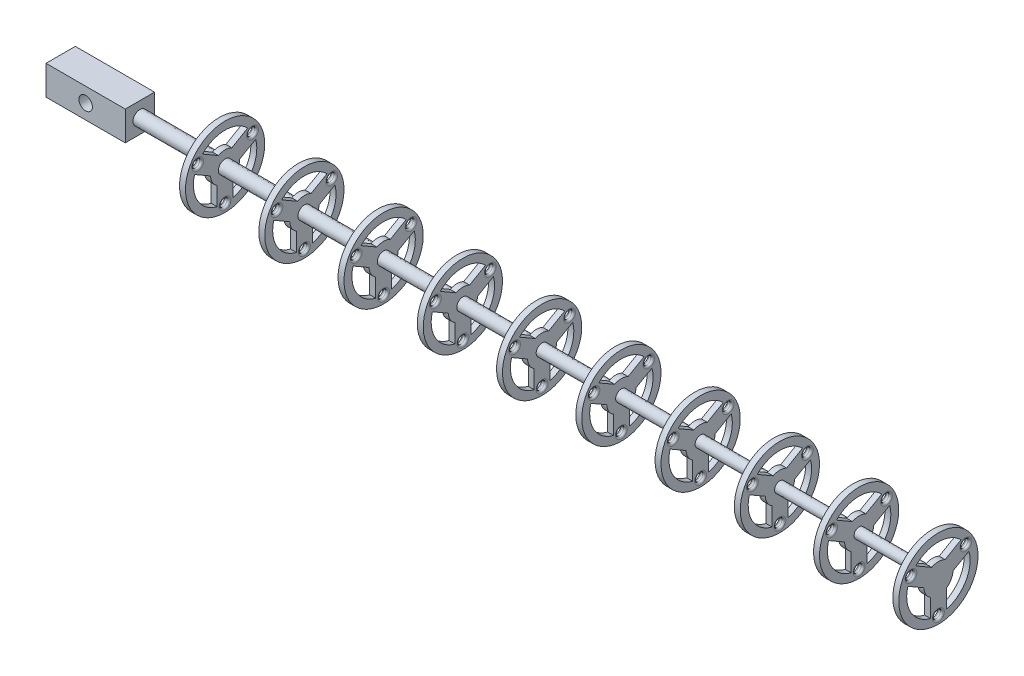
SolidWorks part; units mm, degrees
ref_plane "Front Plane" through (0, 0, 0) normal (0, 0, 1) x (1, 0, 0)
ref_plane "Top Plane" through (0, 0, 0) normal (0, 1, 0) x (1, 0, 0)
ref_plane "Right Plane" through (0, 0, 0) normal (1, 0, 0) x (0, 0, -1)
sketch "Sketch2" plane through (0, 0, 0) normal (0, 0, 1) x (1, 0, 0)
  line L0 (0, 1.75) -> (200, 1.25)
  line L1 (0, -11) -> (0, 11) construction
  line L2 (200, 1.25) -> (200, 0)
  line L3 (200, 0) -> (0, 0)
  line L4 (0, 0) -> (0, 1.75)
  dimension "D1" = 1.75
  dimension "D2" = 200
  dimension "D3" = 1.25
revolve "Revolve1" add sketch "Sketch2" angle 360 about L3
ref_axis "Axis1" through (-3.9062, 0, 0) along (1, 0, 0)
sketch "Sketch3" plane through (0, 0, 0) normal (0, 0, 1) x (1, 0, 0)
  line L0 (20, 0) -> (20, 10)
  line L1 (20, 10) -> (21.5, 10)
  line L2 (21.5, 10) -> (21.5, 0)
  line L3 (21.5, 0) -> (20, 0)
  line L4 (0, -11) -> (0, 11) construction
  dimension "D1" = 1.5
  dimension "D2" = 10
  dimension "D3" = 20
revolve "Revolve2" add sketch "Sketch3" angle 360 about L3
sketch "Sketch5" plane through (21.5, 0, 0) normal (1, 0, 0) x (0, 0, -1)
  line L0 (0, -8) -> (0, 0) construction
  line L1 (0, 0) -> (6.9282, 4) construction
  line L2 (-6.9282, 4) -> (0, 0) construction
  line L3 (0, 11) -> (0, -11) construction
  line L4 (-5.7082, 5.605) -> (-1.692, 3.2863)
  line L5 (1.692, 3.2863) -> (5.7082, 5.605)
  line L6 (2, -3.1084) -> (2, -7.746)
  line L7 (7.7082, 2.1409) -> (3.692, -0.1778)
  line L8 (-3.692, -0.1778) -> (-7.7082, 2.1409)
  line L9 (-2, -7.746) -> (-2, -3.1084)
  circle A0 centre (0, -8) radius 1
  circle A1 centre (6.9282, 4) radius 1
  circle A2 centre (-6.9282, 4) radius 1
  arc A3 (-5.7082, 5.605) -> (5.7082, 5.605) centre (0, 0) cw
  circle A6 centre (0, 0) radius 10 construction
  arc A8 (-1.692, 3.2863) -> (1.692, 3.2863) centre (0, 0) cw
  circle A9 centre (0, 0) radius 1.6962 construction
  arc A10 (7.7082, 2.1409) -> (2, -7.746) centre (0, 0) cw
  arc A11 (3.692, -0.1778) -> (2, -3.1084) centre (0, 0) cw
  arc A12 (-2, -7.746) -> (-7.7082, 2.1409) centre (0, 0) cw
  arc A13 (-2, -3.1084) -> (-3.692, -0.1778) centre (0, 0) cw
  point P29 (0, 0)
  dimension "D2" = 2
  dimension "D1" = 8
  dimension "D3" = 120
  dimension "D4" = 120
  dimension "D6" = 2
  dimension "D7" = 2
  dimension "D5" = 2
  dimension "D8" = 3
extrude "Cut-Extrude1" cut sketch "Sketch5" against normal up to next
fillet "Fillet1" radius 0.5 6 edges at (20, 3, -6.9282) (20, -9, 0) (21.5, -7, 0) (21.5, 5, -6.9282) (20, 3, 6.9282) (21.5, 5, 6.9282)
pattern_linear "LPattern1" count 10 spacing 20 along (1, 0, 0) of "Revolve2", "Cut-Extrude1", "Fillet1"
sketch "Sketch16" plane through (0, 0, 0) normal (-1, 0, 0) x (0, 0, 1)
  line L1 (-3.7, -3.7) -> (3.7, -3.7)
  line L2 (-3.7, -3.7) -> (-3.7, 3.7)
  line L3 (-3.7, 3.7) -> (3.7, 3.7)
  line L4 (3.7, -3.7) -> (3.7, 3.7)
  line L5 (-3.7, -3.7) -> (3.7, 3.7) construction
  line L6 (-3.7, 3.7) -> (3.7, -3.7) construction
  point P0 (0, 0)
  dimension "D1" = 7.4
extrude "Boss-Extrude1" add sketch "Sketch16" along normal blind 20
sketch "Sketch19" plane through (0, 0, -3.7) normal (0, 0, -1) x (-1, 0, 0)
  line L0 (3.9062, 0) -> (-200, 0) construction
  line L1 (20, 3.7) -> (0, 3.7) construction
  line L2 (20, 3.7) -> (20, -3.7) construction
  point P0 (10, 0)
  point P7 (10, 3.7)
  point P10 (20, 0)
hole_wizard "M3 Clearance Hole1" positions "Sketch19" profile "Sketch18" hole size "M3" standard "ANSI Metric" end condition through all
sketch "Sketch18" plane through (-10, 0, -3.7) normal (1, 0, 0) x (0, 1, 0)
  line L0 (0, 0) -> (0, 13.7)
  line L1 (0, 13.7) -> (1.7, 13.7)
  line L2 (1.7, 13.7) -> (1.7, 0.025)
  line L3 (1.7, 0.025) -> (1.725, 0)
  line L5 (1.725, 0) -> (0, 0)
  line L6 (-1.7, 0.025) -> (-1.725, 0) construction
  line L11 (0, -6.35) -> (0, 107.95) construction
  dimension "Thru Hole Dia." = 3.4
  dimension "Thru Hole Depth" = 13.7
  dimension "Near C'Sink Dia." = 3.45
  dimension "Near C'Sink Angle" = 90
equation "\"R_initial\"= 1.75"
equation "\"D1@Sketch2\"=\"R_initial\""
equation "\"R_distal\"= 1.25"
equation "\"D3@Sketch2\"=\"R_distal\""
equation "\"L\"=200"
equation "\"D2@Sketch2\"=\"L\""
equation "\"disk_thickness\"= 1.5"
equation "\"D1@Sketch3\"=\"disk_thickness\""
equation "\"disk_radius\"= 10"
equation "\"D2@Sketch3\"=\"disk_radius\""
equation "\"disk_spacing_initial\"= 20"
equation "\"D3@Sketch3\"=\"disk_spacing_initial\""
equation "\"tendon_routing_radius\"= 8"
equation "\"D1@Sketch5\"=\"tendon_routing_radius\""
equation "\"tendon_routing_hole_radius\"=2"
equation "\"D2@Sketch5\"=\"tendon_routing_hole_radius\""
equation "\"tendon_routing_hole_fillet\"=0.5"
equation "\"D1@Fillet1\"=\"tendon_routing_hole_fillet\""
equation "\"inter_disk_spacing\"= 20"
equation "\"D3@LPattern1\"=\"inter_disk_spacing\""
equation "\"num_disk\"= 10"
equation "\"D1@LPattern1\"=\"num_disk\""
